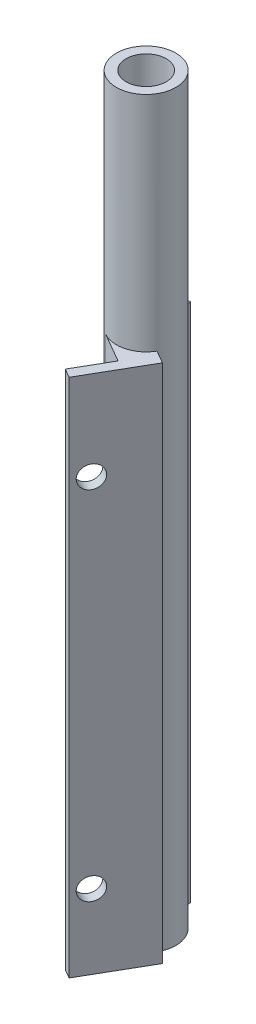
SolidWorks part; units mm, degrees
ref_plane "Front Plane" through (0, 0, 0) normal (0, 0, 1) x (1, 0, 0)
ref_plane "Top Plane" through (0, 0, 0) normal (0, 1, 0) x (1, 0, 0)
ref_plane "Right Plane" through (0, 0, 0) normal (1, 0, 0) x (0, 0, -1)
sketch "Sketch1" plane through (0, 0, 0) normal (0, 1, 0) x (1, 0, 0)
  circle A0 centre (0, 0) radius 5.08
  dimension "D1" = 10.16
extrude "Boss-Extrude1" add sketch "Sketch1" along normal blind 127
sketch "Sketch2" plane through (0, 0, 0) normal (0, -1, 0) x (1, 0, 0)
  circle A0 centre (0, 0) radius 3.429
  dimension "D1" = 6.858
extrude "Cut-Extrude1" cut sketch "Sketch2" against normal through all
sketch "Sketch3" plane through (0, 0, 0) normal (0, -1, 0) x (1, 0, 0)
  line L0 (0, 0) -> (0, -5.08) construction
  line L1 (0, -5.08) -> (-5.08, -5.08) construction
  line L2 (0, 0) -> (-2.54, 4.3994) construction
  line L3 (0, 0) -> (-5.08, 0) construction
  line L4 (-2.54, 4.3994) -> (1.8594, 6.9394) construction
  line L5 (8.7988, -5.08) -> (-1.4426, 12.6586) construction
  line L7 (0, -5.08) -> (-11.684, -5.08) construction
  line L8 (-1.4426, 12.6586) -> (-5.842, 10.1186)
  line L9 (-11.684, -5.08) -> (-11.684, 0)
  line L10 (-5.842, 10.1186) -> (-2.54, 4.3994)
  line L11 (-11.684, 0) -> (-5.08, 0)
  line L13 (-11.684, -5.08) -> (-11.684, -10.16)
  line L14 (-11.684, -10.16) -> (0, -10.16)
  line L15 (0, -10.16) -> (0, -5.08)
  line L17 (4.3994, 2.54) -> (8.7988, 5.08)
  line L18 (8.7988, 5.08) -> (2.9568, 15.1986)
  line L19 (2.9568, 15.1986) -> (-1.4426, 12.6586)
  arc A0 (-5.08, 0) -> (-2.54, 4.3994) centre (-0.7771, 0.4486) ccw
  circle A1 centre (0, 0) radius 3.429 construction
  circle A2 centre (0, 0) radius 5.08 construction
  arc A3 (4.3994, 2.54) -> (0, -5.08) centre (0, 0) cw
  point P9 (0, -5.08)
  dimension "D1" = 60
  dimension "D2" = 6.604
  dimension "D3" = 6.604
  dimension "D4" = 5.08
  dimension "D5" = 5.08
extrude "Boss-Extrude2" add sketch "Sketch3" against normal blind 88.9
sketch "Sketch4" plane through (0, 0, 0) normal (0, 0, 1) x (1, 0, 0)
  line L1 (-5.08, 88.9) -> (-5.08, 0) construction
  line L2 (-5.08, 88.9) -> (-11.684, 88.9) construction
  circle A0 centre (-8.89, 81.28) radius 1.905
  circle A1 centre (-8.89, 20.32) radius 1.905
  dimension "D3" = 3.81
  dimension "D1" = 7.62
  dimension "D2" = 68.58
  dimension "D4" = 3.81
extrude "Hole Cuts 1" cut sketch "Sketch4" against normal up to next
sketch "Sketch7" plane through (0, 0, 0) normal (0.866, 0, 0.5) x (0.5, 0, -0.866)
  line L1 (-5.08, 88.9) -> (-5.08, 0) construction
  line L3 (-2.54, 88.9) -> (-5.842, 88.9) construction
  line L5 (0, 88.9) -> (-11.684, 88.9) construction
  circle A0 centre (-8.89, 73.66) radius 1.905
  circle A1 centre (-8.89, 12.7) radius 1.905
  dimension "D2" = 3.81
  dimension "D1" = 3.81
  dimension "D3" = 15.24
  dimension "D4" = 76.2
extrude "Hole Cuts 2" cut sketch "Sketch7" along normal up to next
sketch "Sketch8" plane through (0, 0, 0) normal (0, -1, 0) x (1, 0, 0)
  line L0 (-5.842, 10.1186) -> (-1.8825, 12.4046)
  line L1 (2.9568, 15.1986) -> (-5.842, 10.1186) construction
  line L2 (-11.684, 0) -> (-11.684, -4.572)
  line L3 (-11.684, 0) -> (-11.684, -10.16) construction
  line L4 (-5.842, 10.1186) -> (-2.54, 4.3994)
  line L5 (-11.684, 0) -> (-5.08, 0)
  line L6 (-1.8825, 12.4046) -> (1.4195, 6.6854)
  line L7 (1.4195, 6.6854) -> (-2.54, 4.3994)
  line L8 (-11.684, -4.572) -> (-5.08, -4.572)
  line L9 (-5.08, -4.572) -> (-5.08, 0)
  dimension "D1" = 4.572
extrude "Cut-Extrude7" cut sketch "Sketch8" against normal up to next
sketch "Sketch9" plane through (0, 0, -10.16) normal (0, 0, -1) x (-1, 0, 0)
  line L1 (11.684, 88.9) -> (0, 88.9)
  line L2 (11.684, 88.9) -> (11.684, 0)
  line L3 (11.684, 0) -> (0, 0)
  line L4 (0, 88.9) -> (0, 0)
extrude "Cut-Extrude8" cut sketch "Sketch9" against normal blind 2.54
sketch "Sketch10" plane through (8.7988, 0, 5.08) normal (0.866, 0, 0.5) x (0.5, 0, -0.866)
  line L1 (-11.684, 0) -> (0, 0)
  line L2 (-11.684, 0) -> (-11.684, 88.9)
  line L3 (-11.684, 88.9) -> (0, 88.9)
  line L4 (0, 0) -> (0, 88.9)
extrude "Cut-Extrude9" cut sketch "Sketch10" against normal blind 2.54
sketch "Sketch11" plane through (0, 0, -4.572) normal (0, 0, 1) x (1, 0, 0)
  line L1 (-11.684, 88.9) -> (-5.08, 88.9)
  line L2 (-11.684, 88.9) -> (-11.684, 0)
  line L3 (-11.684, 0) -> (-5.08, 0)
  line L4 (-5.08, 88.9) -> (-5.08, 0)
extrude "Cut-Extrude10" cut sketch "Sketch11" against normal blind 1.27
sketch "Sketch13" plane through (3.9595, 0, 2.286) normal (-0.866, 0, -0.5) x (-0.5, 0, 0.866)
  line L1 (5.08, 0) -> (11.684, 0)
  line L2 (5.08, 0) -> (5.08, 88.9)
  line L3 (5.08, 88.9) -> (11.684, 88.9)
  line L4 (11.684, 0) -> (11.684, 88.9)
extrude "Cut-Extrude11" cut sketch "Sketch13" against normal blind 1.27
